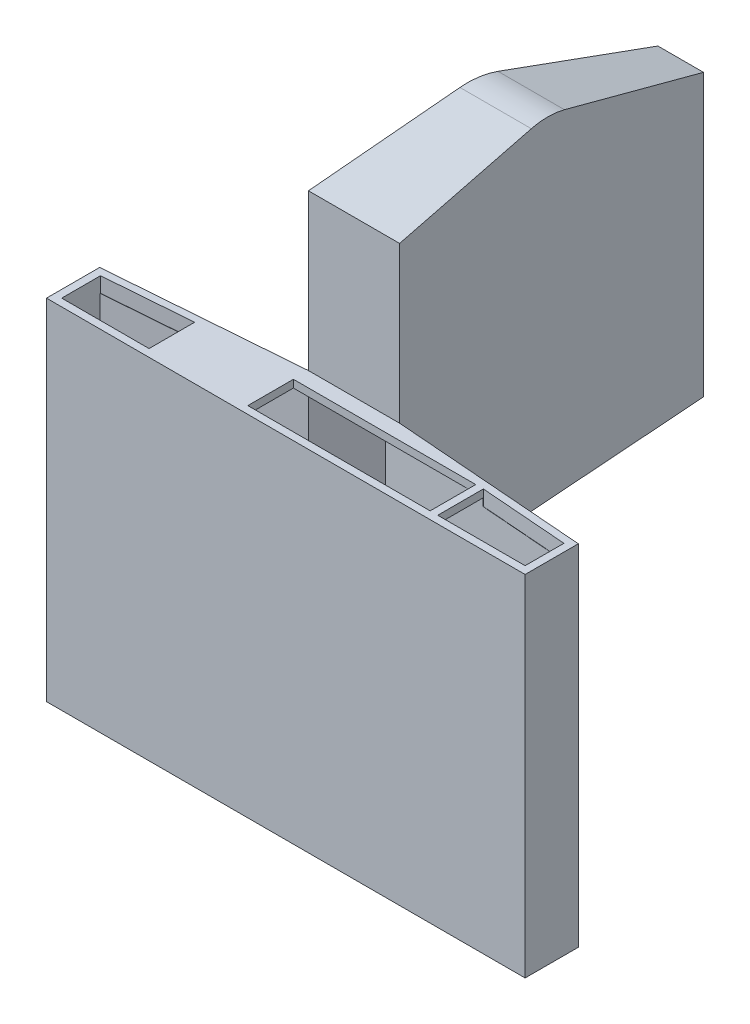
SolidWorks part; units mm, degrees
ref_plane "Front Plane" through (0, 0, 0) normal (0, 0, 1) x (1, 0, 0)
ref_plane "Top Plane" through (0, 0, 0) normal (0, 1, 0) x (1, 0, 0)
ref_plane "Right Plane" through (0, 0, 0) normal (1, 0, 0) x (0, 0, -1)
sketch "Sketch2" plane through (0, 0, 0) normal (0, 1, 0) x (1, 0, 0)
  line L0 (-18.9886, 28.3829) -> (-4.9886, 29.4702)
  line L1 (-30.4886, 20.4898) -> (32.5114, 20.4898)
  line L2 (-30.4886, 20.4898) -> (-30.4886, 27.4898)
  line L5 (-1.9886, 72.4702) -> (4.0114, 72.4702)
  line L10 (-1.9886, 72.4702) -> (-4.9886, 29.4702)
  line L17 (4.0114, 72.4702) -> (7.0114, 29.4702)
  line L22 (32.5114, 20.4898) -> (32.5114, 27.4898)
  line L23 (-30.4886, 27.4898) -> (-18.9886, 28.3829)
  line L25 (7.0114, 29.4702) -> (32.5114, 27.4898)
  dimension "D4" = 43
  dimension "D5" = 25.5
extrude "Boss-Extrude1" add sketch "Sketch2" along normal blind 70 contours L0 L10 L5 L17 L25 L22 L1 L2 L23
sketch "Sketch26" plane through (0, 70, 0) normal (0, 1, 0) x (1, 0, 0)
  line L0 (-4.9886, 29.4702) -> (7.0114, 29.4702)
  line L1 (7.0114, 29.4702) -> (32.5114, 27.4898)
  line L2 (32.5114, 27.4898) -> (32.5114, 20.4898)
  line L3 (32.5114, 20.4898) -> (-30.4886, 20.4898)
  line L4 (-30.4886, 20.4898) -> (-30.4886, 27.4898)
  line L5 (-30.4886, 27.4898) -> (-4.9886, 29.4702)
extrude "Cut-Extrude5" cut sketch "Sketch26" against normal blind 24
sketch "Sketch7" plane through (0, 0, 0) normal (1, 0, 0) x (0, 0, -1)
  line L0 (20.4898, 70) -> (20.4898, 65)
  line L1 (20.4898, 45) -> (20.4898, 70) construction
  line L2 (20.4898, 65) -> (50.4898, 70)
  line L3 (72.4702, 70) -> (29.4702, 70) construction
  line L4 (50.4898, 70) -> (20.4898, 70)
  line L5 (50.4898, 70) -> (72.4702, 70)
  line L6 (72.4702, 70) -> (72.4702, 63)
  line L7 (72.4702, 63) -> (50.4898, 70)
  dimension "D1" = 30
  dimension "D2" = 5
  dimension "D3" = 7
extrude "Cut-Extrude4" cut sketch "Sketch7" against normal blind 50 and the other way blind 50 contours L2 L4 L0 | L7 L6 L5 region at (0, 68.3333, -30.4898) region at (0, 67.6667, -65.1434)
shell "Shell2" thickness 1 removed face at (1.0114, 0, -37.48)
fillet "Fillet1" radius 10 1 edges at (1.0114, 70, -50.4898)
sketch "Sketch6" plane through (0, 0, 0) normal (0, -1, 0) x (1, 0, 0)
  line L0 (-4.9886, -29.4702) -> (7.0114, -29.4702)
  line L1 (7.0114, -29.4702) -> (4.0114, -72.4702)
  line L2 (4.0114, -72.4702) -> (-1.9886, -72.4702)
  line L3 (-1.9886, -72.4702) -> (-4.9886, -29.4702)
extrude "Cut-Extrude3" cut sketch "Sketch6" against normal blind 26
sketch "Sketch4" plane through (0, 45, 0) normal (0, 1, 0) x (1, 0, 0)
  line L0 (1.0114, 72.4702) -> (1.0114, 20.4898) construction
  line L1 (-30.4886, 27.4898) -> (-30.4886, 20.4898) construction
  line L2 (-29.4886, 26.5966) -> (-17.9886, 27.4898)
  line L24 (-30.4886, 20.4898) -> (32.5114, 20.4898) construction
  line L28 (-4.9886, 29.4702) -> (-30.4886, 27.4898) construction
  line L36 (-29.4886, 21.4898) -> (-29.4886, 26.5966)
  line L38 (-17.9886, 27.4898) -> (-17.9886, 21.4898)
  line L40 (31.5114, 21.4898) -> (20.0114, 21.4898)
  line L42 (-29.4886, 21.4898) -> (-17.9886, 21.4898)
  line L43 (20.0114, 27.4898) -> (20.0114, 21.4898)
  line L44 (31.5114, 21.4898) -> (31.5114, 26.5966)
  line L45 (31.5114, 26.5966) -> (20.0114, 27.4898)
  line L46 (-4.9886, 29.4702) -> (-4.9886, 20.4898) construction
  line L47 (-4.9886, 21.4898) -> (19.0114, 21.4898)
  line L48 (19.0114, 21.4898) -> (19.0114, 27.4898)
  line L49 (19.0114, 27.4898) -> (-4.9886, 27.4898)
  line L50 (-4.9886, 27.4898) -> (-4.9886, 21.4898)
  line L51 (7.0114, 29.4702) -> (-4.9886, 29.4702) construction
  dimension "D1" = 1
  dimension "D2" = 1
  dimension "D3" = 1
  dimension "D4" = 11.5
  dimension "D5" = 1
  dimension "D6" = 6
extrude "Cut-Extrude2" cut sketch "Sketch4" against normal blind 1 and the other way blind 1
